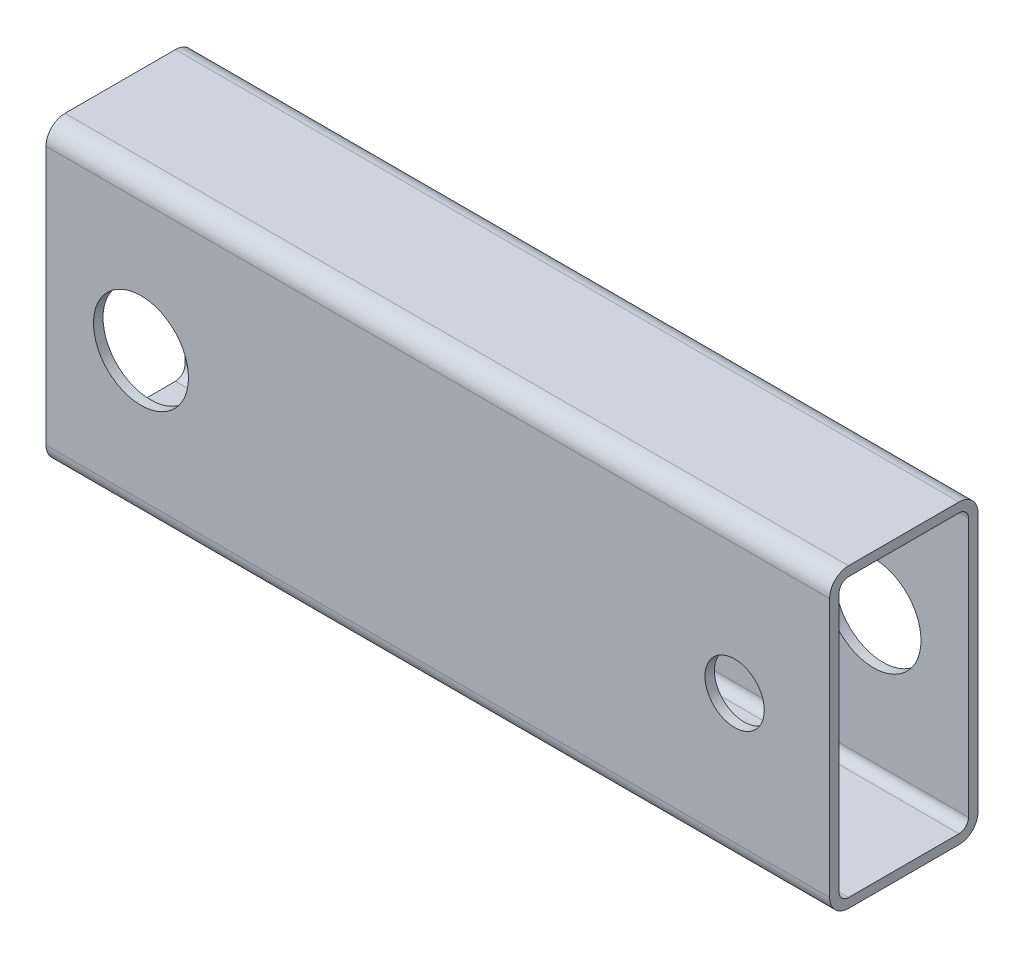
SolidWorks part; units mm, degrees
note: The reader was unsure of these and kept them because the rebuilt part matched: shared geometry of "Sketch2<3>", "Sketch2<4>".
material "Plain Carbon Steel"
ref_plane "Front Plane" through (0, 0, 0) normal (0, 0, 1) x (1, 0, 0)
ref_plane "Top Plane" through (0, 0, 0) normal (0, 1, 0) x (1, 0, 0)
ref_plane "Right Plane" through (0, 0, 0) normal (1, 0, 0) x (0, 0, -1)
sketch3d "3DSketch1"
  line L0 (0, 0, 0) -> (132, 0, 0)
  dimension "D1" = 132
other "Rectangular tube 2 50 X 25 X 1.6(1)" corner treatment miter
ref_plane "Plane1" through (0, 0, 0) normal (1, 0, 0) x (0, 0, -1)
sketch "Sketch14" plane through (0, 0, 0) normal (1, 0, 0) x (0, 0, -1)
  line L0 (-9.3, -23.4) -> (9.3, -23.4)
  line L1 (-10.9, -21.8) -> (-10.9, 21.8)
  line L2 (9.3, 23.4) -> (-9.3, 23.4)
  line L3 (10.9, 21.8) -> (10.9, -21.8)
  line L4 (-9.3, -25) -> (9.3, -25)
  line L5 (-12.5, -21.8) -> (-12.5, 21.8)
  line L6 (9.3, 25) -> (-9.3, 25)
  line L7 (12.5, 21.8) -> (12.5, -21.8)
  arc A0 (12.5, 21.8) -> (9.3, 25) centre (9.3, 21.8) ccw
  arc A1 (9.3, -25) -> (12.5, -21.8) centre (9.3, -21.8) ccw
  arc A2 (-12.5, -21.8) -> (-9.3, -25) centre (-9.3, -21.8) ccw
  arc A3 (-9.3, 25) -> (-12.5, 21.8) centre (-9.3, 21.8) ccw
  arc A4 (-9.3, 23.4) -> (-10.9, 21.8) centre (-9.3, 21.8) ccw
  arc A5 (10.9, 21.8) -> (9.3, 23.4) centre (9.3, 21.8) ccw
  arc A6 (9.3, -23.4) -> (10.9, -21.8) centre (9.3, -21.8) ccw
  arc A7 (-10.9, -21.8) -> (-9.3, -23.4) centre (-9.3, -21.8) ccw
  point P0 (0, 25)
  point P1 (12.5, 0)
  point P2 (0, -25)
  point P3 (-12.5, 0)
  point P4 (-12.5, 25)
  point P5 (12.5, 25)
  point P6 (12.5, -25)
  point P7 (-12.5, -25)
  point P8 (0, 0)
  point P33 (0, 0)
  dimension "D1" = 3.2
  dimension "Thickness" = 1.6
  dimension "V_leg" = 50
  dimension "H_leg" = 25
sketch "Sketch2" plane through (0, 0, 12.5) normal (0, 0, 1) x (1, 0, 0)
  line L0 (-9.6251, 0) -> (105.0203, 0) construction
  line L1 (66, 14) -> (66, 24.8107) construction
  line L2 (0, 21.8) -> (132, -21.8)
  line L4 (0, 21.8) -> (0, -21.8)
  line L5 (0, -21.8) -> (132, -21.8)
  line L6 (132, -21.8) -> (132, 21.8)
  line L7 (132, 21.8) -> (0, 21.8)
  line L8 (0, 21.8) -> (0, -21.8)
  line L9 (0, -21.8) -> (132, -21.8)
  line L10 (132, -21.8) -> (132, 21.8)
  line L11 (132, 21.8) -> (0, 21.8)
  circle A0 centre (16, 0) radius 5
  circle A1 centre (16, 0) radius 16 construction
  circle A2 centre (116, 0) radius 5
  circle A4 centre (16, 0) radius 8
  circle A5 centre (116, 0) radius 8
  point P14 (66, 0)
  dimension "D3" = 10
  dimension "D4" = 32
  dimension "D2" = 3
  dimension "D1" = 0
extrude "Cut-Extrude1" cut sketch "Sketch2" against normal through all contours A0 | A2
extrude "Cut-Extrude2" cut sketch "Sketch2<3>" against normal up to surface (1.6 mm away) contours A4 A0 | A0 up to face at (111, 0, 10.9)
sketch "Sketch2<3>" plane through (0, 0, 12.5) normal (0, 0, 1) x (1, 0, 0) same geometry as "Sketch2"
extrude "Cut-Extrude5" cut sketch "Sketch2<4>" against normal up to surface (1.6 mm away) from surface at -23.4 contours A5 A2 | A2 up to face at (66, 0, -12.5) starting at face at (121, 0, -10.9)
sketch "Sketch2<4>" plane through (0, 0, 12.5) normal (0, 0, 1) x (1, 0, 0) same geometry as "Sketch2"
